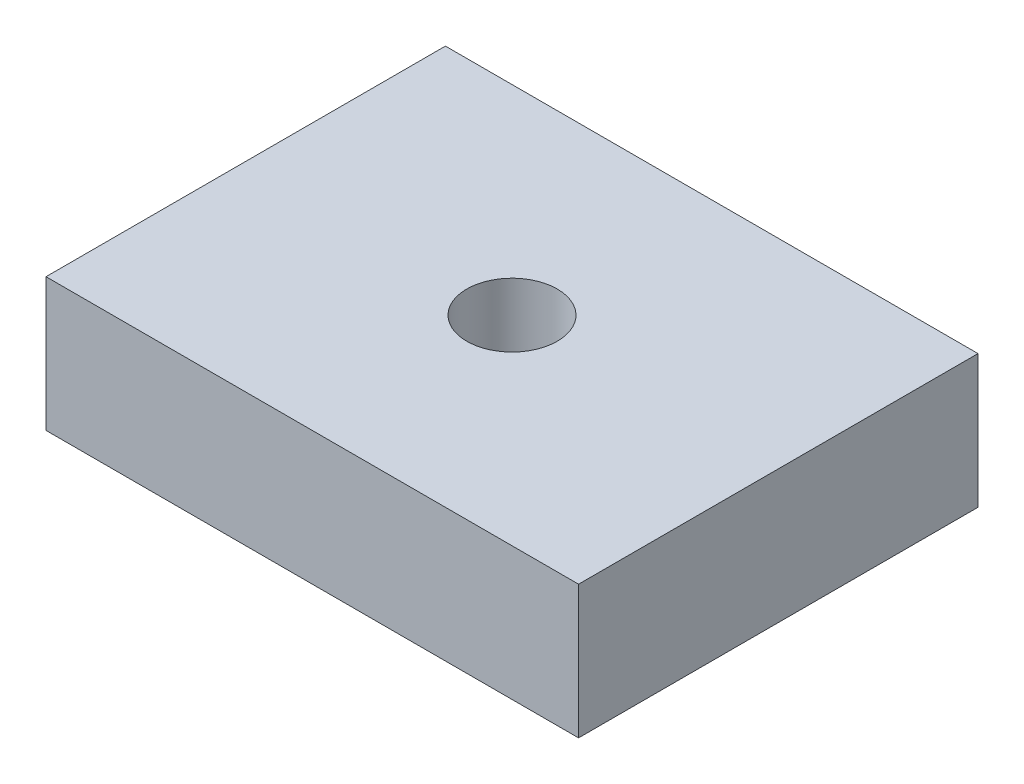
SolidWorks part; units mm, degrees
ref_plane "Front Plane" through (0, 0, 0) normal (0, 0, 1) x (1, 0, 0)
ref_plane "Top Plane" through (0, 0, 0) normal (0, 1, 0) x (1, 0, 0)
ref_plane "Right Plane" through (0, 0, 0) normal (1, 0, 0) x (0, 0, -1)
sketch "Sketch1" plane through (0, 0, 0) normal (0, 1, 0) x (1, 0, 0)
  line L1 (0, 0) -> (20, 0)
  line L2 (0, 0) -> (0, 15)
  line L3 (0, 15) -> (20, 15)
  line L4 (20, 0) -> (20, 15)
  dimension "D1" = 15
  dimension "D2" = 20
extrude "Boss-Extrude1" add sketch "Sketch1" along normal blind 5
hole_wizard "CSK for M3 Flat Head Machine Screw1" positions "3DSketch2" profile "Sketch2" countersink size "M3" standard "ANSI Metric" end condition through all
sketch3d "3DSketch2"
  line L0 (20, 0, -15) -> (0, 0, -15) construction
  line L1 (0, 0, -15) -> (0, 0, 0) construction
  point P0 (10, 0, -7.5)
  dimension "D1" = 7.5
  dimension "D2" = 10
sketch "Sketch2" plane through (10, 0, -7.5) normal (1, 0, 0) x (0, 0, -1)
  line L0 (0, 0) -> (0, 5)
  line L1 (0, 5) -> (1.7, 5)
  line L2 (1.7, 5) -> (1.7, 1.45)
  line L3 (1.7, 1.45) -> (3.15, 0)
  line L5 (3.15, 0) -> (0, 0)
  line L6 (-1.7, 1.45) -> (-3.15, 0) construction
  line L11 (0, -6.35) -> (0, 107.95) construction
  dimension "Thru Hole Dia." = 3.4
  dimension "Thru Hole Depth" = 5
  dimension "Near C'Sink Dia." = 6.3
  dimension "Near C'Sink Angle" = 90
